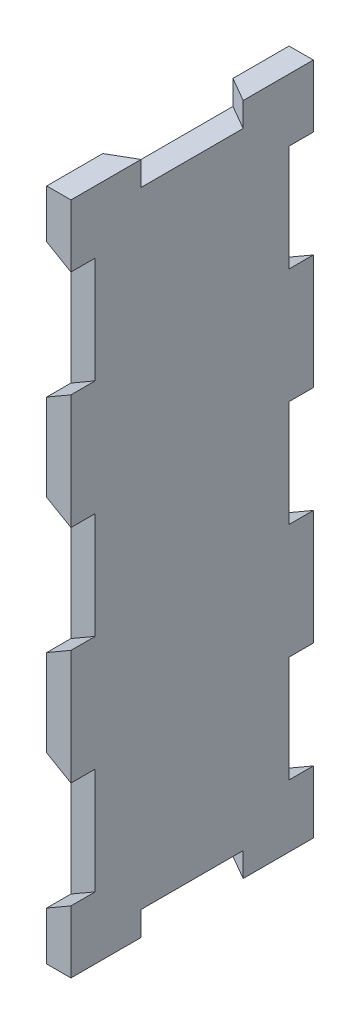
SolidWorks part; units mm, degrees
ref_plane "Front Plane" through (0, 0, 0) normal (1, 0, 0) x (0, 1, 0)
ref_plane "Top Plane" through (0, 0, 0) normal (0, 0, 1) x (0, 1, 0)
ref_plane "Right Plane" through (0, 0, 0) normal (0, 1, 0) x (-1, 0, 0)
sketch "Sketch2" plane through (0, 0, 0) normal (1, 0, 0) x (0, 1, 0)
  line L1 (-69.5, -25) -> (69.5, -25)
  line L2 (-69.5, -25) -> (-69.5, 25)
  line L3 (-69.5, 25) -> (69.5, 25)
  line L4 (69.5, -25) -> (69.5, 25)
  line L5 (-69.5, -25) -> (69.5, 25) construction
  line L6 (-69.5, 25) -> (69.5, -25) construction
  point P0 (0, 0)
  dimension "D1" = 139
  dimension "D2" = 50
extrude "Boss-Extrude1" add sketch "Sketch2" along normal blind 5
sketch "Sketch3" plane through (0, 0, -25) normal (0, 0, -1) x (1, 0, 0)
  line L0 (0, 31.7872) -> (0, 59.5)
  line L1 (0, 59.5) -> (24, 45.6436)
  line L2 (24, 45.6436) -> (0, 31.7872)
  line L3 (0, -27.5) -> (0, 27.5) construction
  line L4 (5, 69.5) -> (0, 69.5) construction
  line L5 (0, -13.8564) -> (0, 13.8564)
  line L6 (0, 13.8564) -> (24, 0)
  line L7 (24, 0) -> (0, -13.8564)
  line L8 (0, -59.5) -> (0, -31.7872)
  line L9 (0, -31.7872) -> (24, -45.6436)
  line L10 (24, -45.6436) -> (0, -59.5)
  line L11 (5, -69.5) -> (0, -69.5) construction
  circle A0 centre (8, 45.6436) radius 8
  dimension "D1" = 16
  dimension "D2" = 0
  dimension "D3" = 10
  dimension "D5" = 10
  dimension "D4" = 3
extrude "Cut-Extrude1" cut sketch "Sketch3" against normal blind 5 contours L7 L5 L6 | L9 L10 L8 | L2 L0 L1
extrude "Cut-Extrude2" cut sketch "Sketch3<3>" against normal blind 5 from offset 45 contours L7 L5 L6 | L9 L10 L8 | L2 L0 L1 offset against normal yes
sketch "Sketch3<3>" plane through (0, 0, -25) normal (0, 0, -1) x (1, 0, 0) same geometry as "Sketch3"
sketch "Sketch6" plane through (0, 69.5, 0) normal (0, 1, 0) x (-1, 0, 0)
  line L0 (0, 13.4234) -> (0, -13.4234)
  line L1 (0, -13.4234) -> (-23.25, 0)
  line L2 (0, 13.4234) -> (-23.25, 0)
  line L3 (0, 27.5) -> (0, -27.5) construction
  line L4 (-5, 25) -> (0, 25) construction
  circle A0 centre (-7.75, 0) radius 7.75
  dimension "D1" = 0
  dimension "D2" = 25
  dimension "D3" = 15.5
extrude "Cut-Extrude3" cut sketch "Sketch6" against normal blind 5 contours L1 L2 L0
extrude "Cut-Extrude5" cut sketch "Sketch6<3>" against normal blind 5 from offset 134 contours L1 L2 L0 offset against normal yes
sketch "Sketch6<3>" plane through (0, 69.5, 0) normal (0, 1, 0) x (-1, 0, 0) same geometry as "Sketch6"
sketch "Sketch4" plane through (0, 0, 0) normal (-1, 0, 0) x (0, -1, 0)
  line L0 (-35.5, -10) -> (49.5, -10)
  line L1 (49.5, -10) -> (49.5, 10)
  line L2 (49.5, 10) -> (42, 17.5)
  line L3 (42, 17.5) -> (-28, 17.5)
  line L4 (-28, 17.5) -> (-35.5, 10)
  line L5 (-35.5, 10) -> (-35.5, -10)
  line L7 (64.5, -13.4234) -> (64.5, 13.4234) construction
  line L8 (-64.5, -13.4234) -> (-64.5, 13.4234) construction
  line L9 (69.5, 25) -> (69.5, 13.4234) construction
  line L10 (31.7872, -20) -> (59.5, -20) construction
  dimension "D1" = 85
  dimension "D2" = 70
  dimension "D3" = 20
  dimension "D4" = 20
  dimension "D5" = 7.5
  dimension "D6" = 10
  dimension "D7" = 15
  dimension "D8" = 20
  dimension "D9" = 29
  dimension "D10" = 7.5
